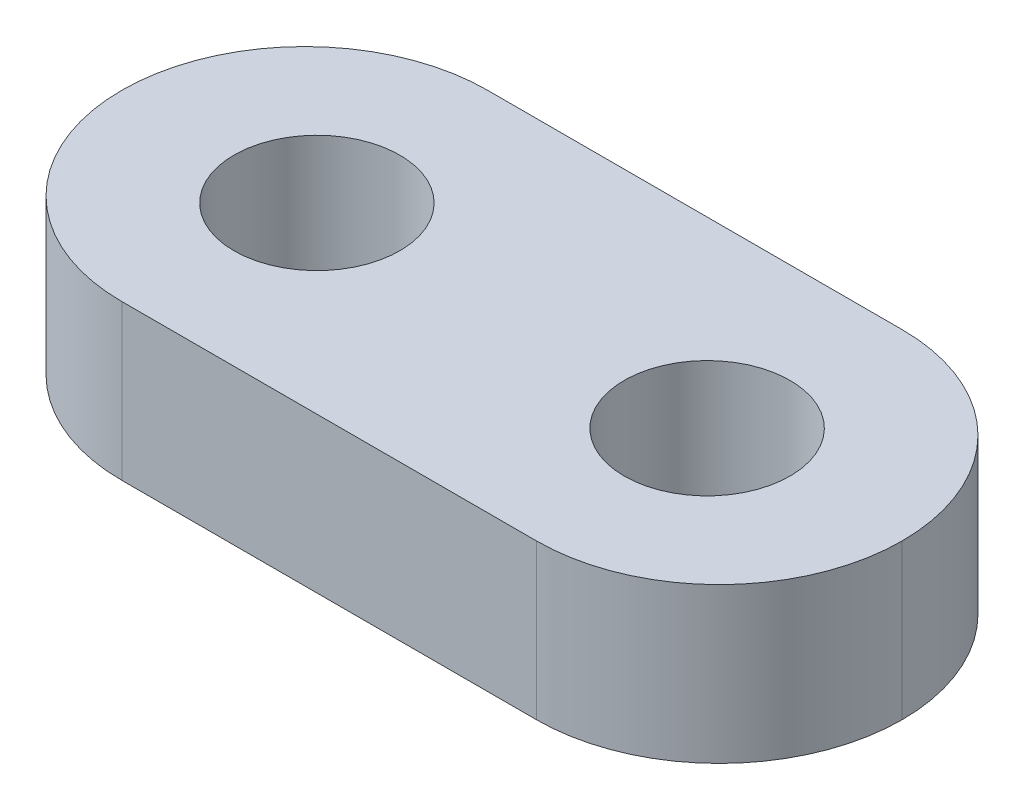
SolidWorks part; units mm, degrees
ref_plane "Front Plane" through (0, 0, 0) normal (0, 0, 1) x (1, 0, 0)
ref_plane "Top Plane" through (0, 0, 0) normal (0, 1, 0) x (1, 0, 0)
ref_plane "Right Plane" through (0, 0, 0) normal (1, 0, 0) x (0, 0, -1)
sketch "Sketch2" plane through (0, 0, 0) normal (0, 1, 0) x (1, 0, 0)
  line L1 (0, 0) -> (32, 0)
  line L2 (0, 0) -> (0, 15)
  line L3 (0, 15) -> (32, 15)
  line L4 (32, 0) -> (32, 15)
  dimension "D1" = 15
  dimension "D2" = 32
extrude "Boss-Extrude1" add sketch "Sketch2" along normal blind 6.35
hole_wizard "Tap Drill for M8x1.25 Tap1" positions "3DSketch1" profile "Sketch4" hole size "M8x1.25" standard "ANSI Metric" end condition through all
sketch3d "3DSketch1"
  line L0 (0, 6.35, -7.5) -> (32, 6.35, -7.5) construction
  line L1 (0, 6.35, -15) -> (0, 6.35, 0) construction
  line L2 (32, 6.35, 0) -> (32, 6.35, -15) construction
  point P7 (8, 6.35, -7.5)
  point P9 (24, 6.35, -7.5)
  dimension "D1" = 8
  dimension "D2" = 8
sketch "Sketch4" plane through (8, 6.35, -7.5) normal (1, 0, 0) x (0, 0, 1)
  line L0 (0, 0) -> (0, 6.35)
  line L1 (0, 6.35) -> (3.4, 6.35)
  line L2 (3.4, 6.35) -> (3.4, 0)
  line L5 (3.4, 0) -> (0, 0)
  line L11 (0, -6.35) -> (0, 107.95) construction
  dimension "Thru Hole Dia." = 6.8
  dimension "Thru Hole Depth" = 6.35
fillet "Fillet1" radius 7.5 4 edges at (32, 3.175, 0) (32, 3.175, -15) (0, 3.175, -15) (0, 3.175, 0)
